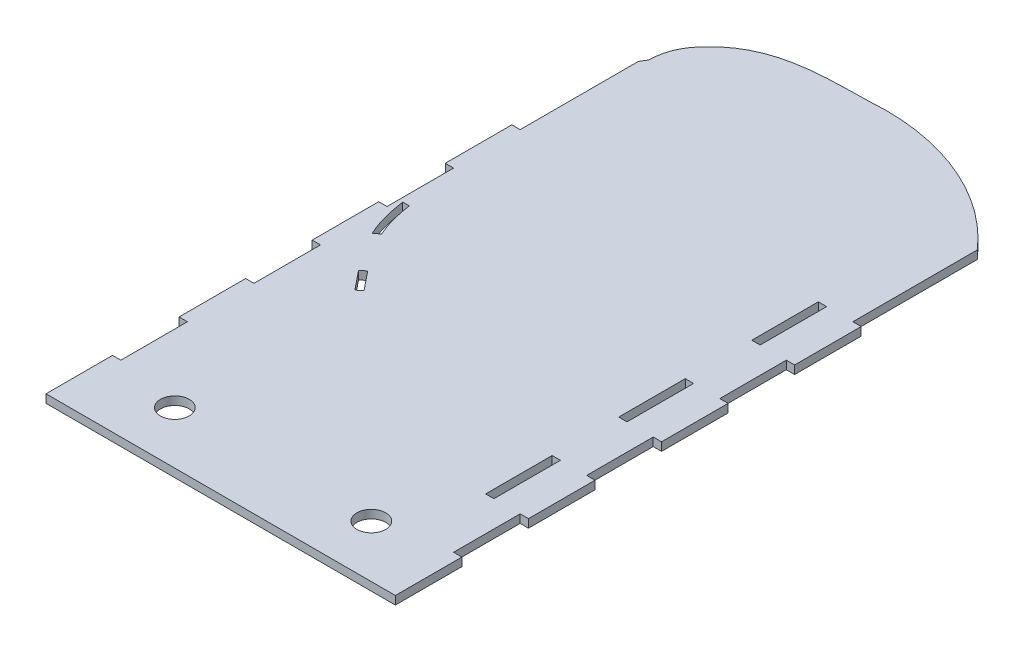
SolidWorks part; units mm, degrees
ref_plane "Front Plane" through (0, 0, 0) normal (0, 0, 1) x (1, 0, 0)
ref_plane "Top Plane" through (0, 0, 0) normal (0, 1, 0) x (1, 0, 0)
ref_plane "Right Plane" through (0, 0, 0) normal (1, 0, 0) x (0, 0, -1)
sketch "Sketch2" plane through (0, 0, 0) normal (0, 1, 0) x (1, 0, 0)
  line L0 (127, 0) -> (127, 40) construction
  line L1 (0, 0) -> (254, 0)
  line L2 (0, 0) -> (0, 508)
  line L3 (0, 508) -> (254, 508)
  line L4 (254, 0) -> (254, 508)
  line L5 (112, 0) -> (112, 40) construction
  line L6 (70.0293, 132.7246) -> (75.0014, 133.2514) construction
  line L8 (3.0464, 262.9295) -> (8.0974, 262.9295)
  line L9 (12.0177, 230.6311) -> (16.1196, 233.6878)
  line L10 (63.9635, 154.4733) -> (68.5195, 156.533) construction
  line L11 (31.3299, 200.9155) -> (35.2571, 204.0102)
  line L12 (42.9806, 186.4099) -> (46.8891, 189.5281)
  circle A0 centre (52, 40) radius 11
  circle A1 centre (202, 40) radius 11
  spline S0 degree 3 poles (0, 358) (10.2414, 318.2744) (-10.3205, 225.9555) (70.6512, 174.3118) (75.0014, 133.2514) knots 0 0 0 0 0.517006 1 1 1 1 construction
  spline S1 degree 3 poles (57.0275, 368.1055) (60.011, 340.8516) (38.8621, 298.2828) (61.0822, 235.4033) (84.5865, 206.7018) (104.9746, 198.8412) knots 0 0 0 0 0.426438 0.676001 1 1 1 1 construction
  spline S2 degree 1 poles (-4.8417, 356.7518) (70.0293, 132.7246) knots 0 0 1 1 construction
  spline S3 degree 3 poles (-4.8417, 356.7518) (-4.2453, 354.4384) (-3.2098, 349.8001) (-1.6146, 340.1963) (-0.4104, 327.7832) (0.2492, 312.4005) (0.7261, 291.8409) (1.4026, 275.812) (2.8811, 264.0829) (3.206, 261.7747) (3.5674, 259.4757) (3.9542, 257.1833) (4.5302, 254.1018) (5.5014, 249.6086) (6.6895, 245.0428) (8.2086, 240.135) (9.6429, 236.1559) (11.2633, 232.2426) (12.5555, 229.4544) (14.3601, 225.8497) (18.1885, 218.946) (23.3984, 211.2859) (29.2816, 203.4962) (32.93, 198.8824) (36.8298, 194.0373) (40.7355, 189.2215) (46.6866, 181.7864) (53.9965, 172.1125) (59.9683, 162.643) (63.1245, 156.3309) (64.1438, 154.0765) (64.4933, 153.279) (64.8362, 152.4792) (65.7137, 150.3629) (66.7102, 147.6655) (67.6191, 144.7625) (68.2641, 142.4625) (68.8611, 140.0122) (69.3531, 137.5307) (69.7433, 135.1238) (69.9343, 133.621) (70.0293, 132.7246) knots 0 0 0 0 0.03125 0.0625 0.125 0.1875 0.25 0.371368 0.378402 0.392471 0.399505 0.406539 0.420608 0.4375 0.462351 0.477976 0.5 0.513677 0.529302 0.537114 0.5625 0.625 0.649179 0.680429 0.696054 0.724459 0.755709 0.8125 0.875 0.898852 0.904562 0.907417 0.910272 0.915981 0.9375 0.948072 0.955885 0.96875 0.980913 0.988548 1 1 1 1 only from (0, 317.7537) to (70.0293, 132.7246) construction
  spline S4 degree 1 poles (35.2571, 204.0102) (46.8891, 189.5281) knots 0 0 1 1
  spline S5 degree 1 poles (31.3299, 200.9155) (42.9806, 186.4099) knots 0 0 1 1
  spline S6 degree 3 poles (3.0464, 262.9295) (4.6075, 251.8412) (7.2857, 240.8284) (12.0177, 230.6311) knots 0 0 0 0 1 1 1 1
  spline S7 degree 3 poles (8.0974, 262.9295) (9.5523, 252.911) (11.965, 242.952) (16.1196, 233.6878) knots 0 0 0 0 1 1 1 1
  spline S8 degree 3 poles (68.5195, 156.533) (70.3934, 152.3928) (73.1628, 144.7538) (74.6292, 136.7727) (75.0014, 133.2514) knots 0 0 0 0 0.562151 1 1 1 1 construction
  spline S9 degree 3 poles (63.9635, 154.4733) (65.5406, 150.9864) (68.1883, 143.8779) (69.6381, 136.4314) (70.0293, 132.7246) knots 0 0 0 0 0.506681 1 1 1 1 construction
  dimension "D3" = 22
  dimension "D1" = 508
  dimension "D2" = 254
  dimension "D4" = 40
  dimension "D5" = 15
  dimension "D6" = 60
  dimension "D7" = 150
  dimension "D8" = 5
extrude "Boss-Extrude1" add sketch "Sketch2" along normal blind 6.35
sketch "Sketch3" plane through (0, 6.35, 0) normal (0, 1, 0) x (1, 0, 0)
  line L0 (127, 508) -> (127, 338.6667) construction
  line L1 (254, 508) -> (0, 508) construction
  line L2 (127, 338.6667) -> (127, 169.3333) construction
  line L3 (127, 169.3333) -> (127, 0) construction
  line L4 (0, 0) -> (254, 0) construction
  line L5 (254, 0) -> (254, 508) construction
  line L6 (254, 508) -> (127, 508)
  line L7 (254, 450.6701) -> (254, 508)
  arc A1 (127, 508) -> (254, 450.6701) centre (127, 338.6667) cw
extrude "Cut-Extrude1" cut sketch "Sketch3" against normal up to next
sketch "Sketch5" plane through (0, 6.35, 0) normal (0, 1, 0) x (1, 0, 0)
  line L0 (254, 450.6701) -> (0, 450.6701) construction
  line L1 (0, 508) -> (0, 0) construction
  line L2 (3, 450.6701) -> (0, 445.8071)
  line L3 (0, 508) -> (0, 445.8071)
  line L6 (0, 508) -> (0, 526.7662)
  line L7 (0, 526.7662) -> (127, 526.7662)
  line L8 (127, 508) -> (127, 526.7662)
  circle A0 centre (45, 450.6701) radius 22 construction
  arc A2 (16.9934, 481.9692) -> (3, 450.6701) centre (45, 450.6701) ccw
  circle A3 centre (45, 450.6701) radius 42 construction
  spline S0 degree 3 poles (16.9934, 481.9692) (44.7711, 511.7661) (91.2093, 505.8566) (127, 508) knots 0 0 0 0 1 1 1 1
  dimension "D1" = 44
  dimension "D3" = 45
  dimension "D2" = 20
extrude "Cut-Extrude2" cut sketch "Sketch5" against normal up to next
sketch "Sketch7" plane through (0, 0, 0) normal (0, -1, 0) x (1, 0, 0)
  line L1 (254, 0) -> (260.35, 0)
  line L2 (254, 0) -> (254, -50.8)
  line L3 (254, -50.8) -> (260.35, -50.8)
  line L4 (260.35, 0) -> (260.35, -50.8)
  line L5 (0, 0) -> (-6.35, 0)
  line L6 (0, 0) -> (0, -50.8)
  line L7 (0, -50.8) -> (-6.35, -50.8)
  line L8 (-6.35, 0) -> (-6.35, -50.8)
  dimension "D1" = 6.35
  dimension "D2" = 50.8
  dimension "D3" = 6.35
  dimension "D4" = 50.8
extrude "Boss-Extrude2" add sketch "Sketch7" against normal up to surface (6.35 mm away) up to face at (9.7017, 6.35, -247.9266)
pattern_linear "LPattern1" count 4 spacing 101.6 along (0, 0, -1) of "Boss-Extrude2"
sketch "Sketch8" plane through (0, 6.35, 0) normal (0, 1, 0) x (1, 0, 0)
  line L0 (254, 152.4) -> (254, 203.2) construction
  line L5 (234, 152.4) -> (227.65, 152.4)
  line L7 (234, 152.4) -> (234, 101.6)
  line L9 (234, 101.6) -> (227.65, 101.6)
  line L10 (227.65, 152.4) -> (227.65, 101.6)
  line L11 (254, 101.6) -> (260.35, 101.6) construction
  line L12 (260.35, 101.6) -> (260.35, 152.4) construction
  dimension "D1" = 20
extrude "Cut-Extrude3" cut sketch "Sketch8" against normal up to next
pattern_linear "LPattern2" count 3 spacing 101.6 along (0, 0, -1) of "Cut-Extrude3"
sketch "Slider" plane through (0, 6.35, 6.35) normal (0, 1, 0) x (1, 0, 0)
  line L0 (0, 452.1571) -> (0, 361.95) construction
  line L6 (54.1176, 177.8402) -> (58.2442, 180.6634) construction
  spline S0 degree 3 poles (0, 364.2407) (10.0932, 324.5031) (-6.7408, 249.3382) (44.5453, 200.6868) (58.2442, 180.6634) knots 0 0 0 0 0.63201 1 1 1 1 construction
  spline S1 degree 3 poles (57.0275, 368.1055) (60.011, 340.8516) (38.8621, 298.2828) (61.0822, 235.4033) (84.5865, 206.7018) (104.9746, 198.8412) knots 0 0 0 0 0.426438 0.676001 1 1 1 1 construction
  spline S2 degree 1 poles (-4.8461, 363.0098) (54.1176, 177.8402) knots 0 0 1 1 construction
  spline S3 degree 3 poles (-4.8461, 363.0098) (-4.3659, 361.1191) (-3.5097, 357.3301) (-2.1229, 349.5349) (-0.9477, 339.5089) (-0.1716, 327.1083) (0.3662, 310.2426) (0.7835, 288.8153) (2.7416, 267.6076) (6.4419, 251.188) (10.6067, 239.2328) (16.4686, 227.9252) (23.4848, 217.3517) (31.2063, 207.235) (39.1962, 197.3973) (45.7189, 189.2885) (50.658, 182.7615) (52.9812, 179.5011) (54.1176, 177.8402) knots 0 0 0 0 0.03125 0.0625 0.125 0.1875 0.25 0.375 0.5 0.5625 0.625 0.6875 0.75 0.8125 0.875 0.9375 0.96875 1 1 1 1 only from (0, 321.3493) to (54.1176, 177.8402) construction
  dimension "D8" = 5
